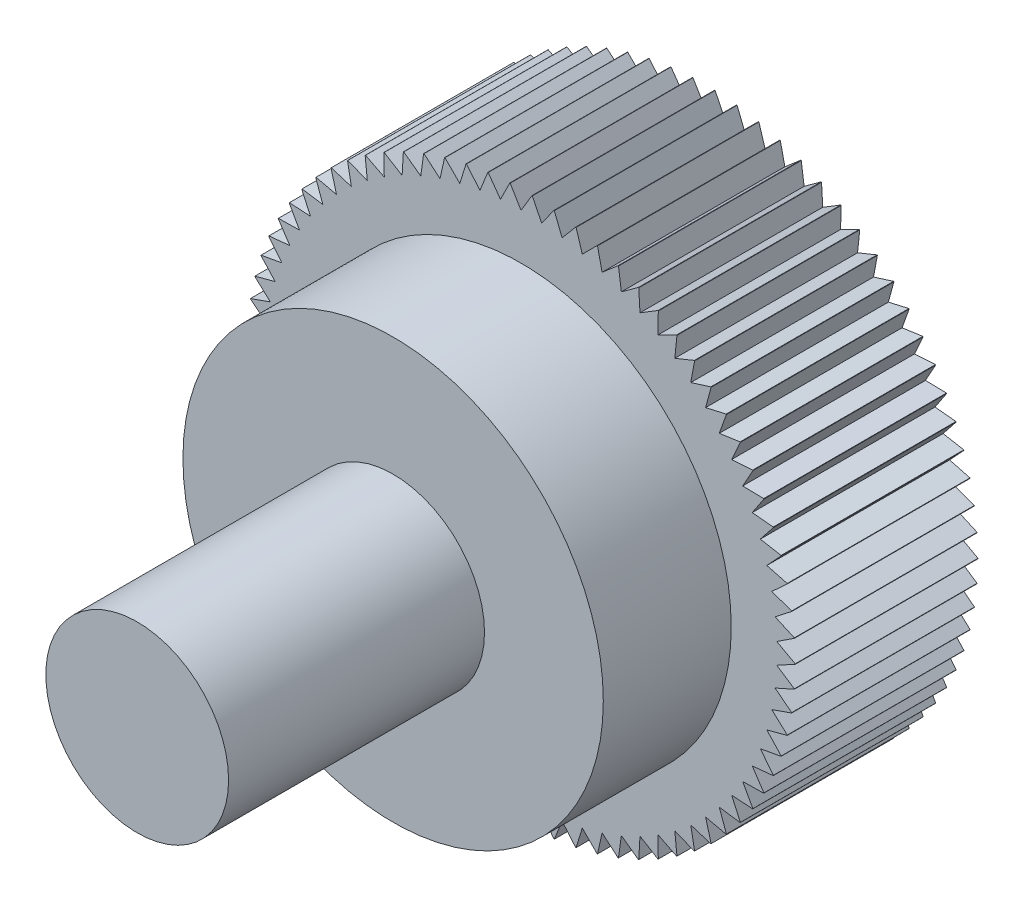
SolidWorks part; units mm, degrees
ref_plane "Front" through (0, 0, 0) normal (0, 0, 1) x (1, 0, 0)
ref_plane "Top" through (0, 0, 0) normal (0, 1, 0) x (1, 0, 0)
ref_plane "Right" through (0, 0, 0) normal (1, 0, 0) x (0, 0, -1)
sketch "Sketch1" plane through (0, 0, 0) normal (0, 0, 1) x (1, 0, 0)
  circle A0 centre (0, 0) radius 7.5
  dimension "D1" = 15
extrude "Extrude1" add sketch "Sketch1" along normal blind 5
sketch "Sketch2" plane through (0, 0, 5) normal (0, 0, 1) x (1, 0, 0)
  circle A0 centre (0, 0) radius 5.75
  dimension "D1" = 11.5
extrude "Extrude2" add sketch "Sketch2" along normal blind 3.5
sketch "Sketch3" plane through (0, 0, 8.5) normal (0, 0, 1) x (1, 0, 0)
  circle A0 centre (0, 0) radius 2.5
  dimension "D1" = 5
extrude "Extrude3" add sketch "Sketch3" along normal blind 7
sketch "Sketch4" plane through (0, 0, 0) normal (0, 0, -1) x (-1, 0, 0)
  line L0 (0, 0) -> (0, 7.5) construction
  line L1 (-0.3, 7.5) -> (0, 7)
  line L2 (0.3, 7.5) -> (0, 7)
  line L3 (-0.3, 7.5) -> (0.3, 7.5)
  line L4 (0.3045, 7.4998) -> (0.5633, 6.9773)
  line L5 (0.9025, 7.4515) -> (0.5633, 6.9773)
  line L6 (0.3045, 7.4998) -> (0.9025, 7.4515)
  line L7 (0.907, 7.451) -> (1.1229, 6.9094)
  line L8 (1.4992, 7.3548) -> (1.1229, 6.9094)
  line L9 (0.907, 7.451) -> (1.4992, 7.3548)
  line L10 (1.5036, 7.3539) -> (1.6752, 6.7966)
  line L11 (2.0862, 7.2103) -> (1.6752, 6.7966)
  line L12 (1.5036, 7.3539) -> (2.0862, 7.2103)
  line L13 (2.0904, 7.209) -> (2.2167, 6.6398)
  line L14 (2.6596, 7.019) -> (2.2167, 6.6398)
  line L15 (2.0904, 7.209) -> (2.6596, 7.019)
  line L16 (2.6638, 7.0174) -> (2.7438, 6.4399)
  line L17 (3.2157, 6.7823) -> (2.7438, 6.4399)
  line L18 (2.6638, 7.0174) -> (3.2157, 6.7823)
  line L19 (3.2198, 6.7803) -> (3.2531, 6.1982)
  line L20 (3.7511, 6.5015) -> (3.2531, 6.1982)
  line L21 (3.2198, 6.7803) -> (3.7511, 6.5015)
  line L22 (3.7549, 6.4993) -> (3.7413, 5.9163)
  line L23 (4.2621, 6.1786) -> (3.7413, 5.9163)
  line L24 (3.7549, 6.4993) -> (4.2621, 6.1786)
  line L25 (4.2657, 6.176) -> (4.2052, 5.5961)
  line L26 (4.7454, 5.8156) -> (4.2052, 5.5961)
  line L27 (4.2657, 6.176) -> (4.7454, 5.8156)
  line L28 (4.7489, 5.8128) -> (4.6419, 5.2396)
  line L29 (5.198, 5.4149) -> (4.6419, 5.2396)
  line L30 (4.7489, 5.8128) -> (5.198, 5.4149)
  line L31 (5.2012, 5.4118) -> (5.0484, 4.8491)
  line L32 (5.6168, 4.9791) -> (5.0484, 4.8491)
  line L33 (5.2012, 5.4118) -> (5.6168, 4.9791)
  line L34 (5.6198, 4.9757) -> (5.4222, 4.4271)
  line L35 (5.9993, 4.511) -> (5.4222, 4.4271)
  line L36 (5.6198, 4.9757) -> (5.9993, 4.511)
  line L37 (6.002, 4.5074) -> (5.7609, 3.9765)
  line L38 (6.3428, 4.0136) -> (5.7609, 3.9765)
  line L39 (6.002, 4.5074) -> (6.3428, 4.0136)
  line L40 (6.3452, 4.0098) -> (6.0622, 3.5)
  line L41 (6.6452, 3.4902) -> (6.0622, 3.5)
  line L42 (6.3452, 4.0098) -> (6.6452, 3.4902)
  line L43 (6.6473, 3.4862) -> (6.3242, 3.0008)
  line L44 (6.9045, 2.9442) -> (6.3242, 3.0008)
  line L45 (6.6473, 3.4862) -> (6.9045, 2.9442)
  line L46 (6.9062, 2.94) -> (6.5451, 2.4822)
  line L47 (7.119, 2.379) -> (6.5451, 2.4822)
  line L48 (6.9062, 2.94) -> (7.119, 2.379)
  line L49 (7.1204, 2.3748) -> (6.7236, 1.9475)
  line L50 (7.2874, 1.7985) -> (6.7236, 1.9475)
  line L51 (7.1204, 2.3748) -> (7.2874, 1.7985)
  line L52 (7.2884, 1.7941) -> (6.8585, 1.4002)
  line L53 (7.4084, 1.2063) -> (6.8585, 1.4002)
  line L54 (7.2884, 1.7941) -> (7.4084, 1.2063)
  line L55 (7.4092, 1.2018) -> (6.949, 0.8438)
  line L56 (7.4815, 0.6062) -> (6.949, 0.8438)
  line L57 (7.4092, 1.2018) -> (7.4815, 0.6062)
  line L58 (7.4818, 0.6018) -> (6.9943, 0.2819)
  line L59 (7.506, 0.0022) -> (6.9943, 0.2819)
  line L60 (7.4818, 0.6018) -> (7.506, 0.0022)
  line L61 (7.506, -0.0022) -> (6.9943, -0.2819)
  line L62 (7.4818, -0.6018) -> (6.9943, -0.2819)
  line L63 (7.506, -0.0022) -> (7.4818, -0.6018)
  line L64 (7.4815, -0.6062) -> (6.949, -0.8438)
  line L65 (7.4092, -1.2018) -> (6.949, -0.8438)
  line L66 (7.4815, -0.6062) -> (7.4092, -1.2018)
  line L67 (7.4084, -1.2063) -> (6.8585, -1.4002)
  line L68 (7.2884, -1.7941) -> (6.8585, -1.4002)
  line L69 (7.4084, -1.2063) -> (7.2884, -1.7941)
  line L70 (7.2874, -1.7985) -> (6.7236, -1.9475)
  line L71 (7.1204, -2.3748) -> (6.7236, -1.9475)
  line L72 (7.2874, -1.7985) -> (7.1204, -2.3748)
  line L73 (7.119, -2.379) -> (6.5451, -2.4822)
  line L74 (6.9062, -2.94) -> (6.5451, -2.4822)
  line L75 (7.119, -2.379) -> (6.9062, -2.94)
  line L76 (6.9045, -2.9442) -> (6.3242, -3.0008)
  line L77 (6.6473, -3.4862) -> (6.3242, -3.0008)
  line L78 (6.9045, -2.9442) -> (6.6473, -3.4862)
  line L79 (6.6452, -3.4902) -> (6.0622, -3.5)
  line L80 (6.3452, -4.0098) -> (6.0622, -3.5)
  line L81 (6.6452, -3.4902) -> (6.3452, -4.0098)
  line L82 (6.3428, -4.0136) -> (5.7609, -3.9765)
  line L83 (6.002, -4.5074) -> (5.7609, -3.9765)
  line L84 (6.3428, -4.0136) -> (6.002, -4.5074)
  line L85 (5.9993, -4.511) -> (5.4222, -4.4271)
  line L86 (5.6198, -4.9757) -> (5.4222, -4.4271)
  line L87 (5.9993, -4.511) -> (5.6198, -4.9757)
  line L88 (5.6168, -4.9791) -> (5.0484, -4.8491)
  line L89 (5.2012, -5.4118) -> (5.0484, -4.8491)
  line L90 (5.6168, -4.9791) -> (5.2012, -5.4118)
  line L91 (5.198, -5.4149) -> (4.6419, -5.2396)
  line L92 (4.7489, -5.8128) -> (4.6419, -5.2396)
  line L93 (5.198, -5.4149) -> (4.7489, -5.8128)
  line L94 (4.7454, -5.8156) -> (4.2052, -5.5961)
  line L95 (4.2657, -6.176) -> (4.2052, -5.5961)
  line L96 (4.7454, -5.8156) -> (4.2657, -6.176)
  line L97 (4.2621, -6.1786) -> (3.7413, -5.9163)
  line L98 (3.7549, -6.4993) -> (3.7413, -5.9163)
  line L99 (4.2621, -6.1786) -> (3.7549, -6.4993)
  line L100 (3.7511, -6.5015) -> (3.2531, -6.1982)
  line L101 (3.2198, -6.7803) -> (3.2531, -6.1982)
  line L102 (3.7511, -6.5015) -> (3.2198, -6.7803)
  line L103 (3.2157, -6.7823) -> (2.7438, -6.4399)
  line L104 (2.6638, -7.0174) -> (2.7438, -6.4399)
  line L105 (3.2157, -6.7823) -> (2.6638, -7.0174)
  line L106 (2.6596, -7.019) -> (2.2167, -6.6398)
  line L107 (2.0904, -7.209) -> (2.2167, -6.6398)
  line L108 (2.6596, -7.019) -> (2.0904, -7.209)
  line L109 (2.0862, -7.2103) -> (1.6752, -6.7966)
  line L110 (1.5036, -7.3539) -> (1.6752, -6.7966)
  line L111 (2.0862, -7.2103) -> (1.5036, -7.3539)
  line L112 (1.4992, -7.3548) -> (1.1229, -6.9094)
  line L113 (0.907, -7.451) -> (1.1229, -6.9094)
  line L114 (1.4992, -7.3548) -> (0.907, -7.451)
  line L115 (0.9025, -7.4515) -> (0.5633, -6.9773)
  line L116 (0.3045, -7.4998) -> (0.5633, -6.9773)
  line L117 (0.9025, -7.4515) -> (0.3045, -7.4998)
  line L118 (0.3, -7.5) -> (0, -7)
  line L119 (-0.3, -7.5) -> (0, -7)
  line L120 (0.3, -7.5) -> (-0.3, -7.5)
  line L121 (-0.3045, -7.4998) -> (-0.5633, -6.9773)
  line L122 (-0.9025, -7.4515) -> (-0.5633, -6.9773)
  line L123 (-0.3045, -7.4998) -> (-0.9025, -7.4515)
  line L124 (-0.907, -7.451) -> (-1.1229, -6.9094)
  line L125 (-1.4992, -7.3548) -> (-1.1229, -6.9094)
  line L126 (-0.907, -7.451) -> (-1.4992, -7.3548)
  line L127 (-1.5036, -7.3539) -> (-1.6752, -6.7966)
  line L128 (-2.0862, -7.2103) -> (-1.6752, -6.7966)
  line L129 (-1.5036, -7.3539) -> (-2.0862, -7.2103)
  line L130 (-2.0904, -7.209) -> (-2.2167, -6.6398)
  line L131 (-2.6596, -7.019) -> (-2.2167, -6.6398)
  line L132 (-2.0904, -7.209) -> (-2.6596, -7.019)
  line L133 (-2.6638, -7.0174) -> (-2.7438, -6.4399)
  line L134 (-3.2157, -6.7823) -> (-2.7438, -6.4399)
  line L135 (-2.6638, -7.0174) -> (-3.2157, -6.7823)
  line L136 (-3.2198, -6.7803) -> (-3.2531, -6.1982)
  line L137 (-3.7511, -6.5015) -> (-3.2531, -6.1982)
  line L138 (-3.2198, -6.7803) -> (-3.7511, -6.5015)
  line L139 (-3.7549, -6.4993) -> (-3.7413, -5.9163)
  line L140 (-4.2621, -6.1786) -> (-3.7413, -5.9163)
  line L141 (-3.7549, -6.4993) -> (-4.2621, -6.1786)
  line L142 (-4.2657, -6.176) -> (-4.2052, -5.5961)
  line L143 (-4.7454, -5.8156) -> (-4.2052, -5.5961)
  line L144 (-4.2657, -6.176) -> (-4.7454, -5.8156)
  line L145 (-4.7489, -5.8128) -> (-4.6419, -5.2396)
  line L146 (-5.198, -5.4149) -> (-4.6419, -5.2396)
  line L147 (-4.7489, -5.8128) -> (-5.198, -5.4149)
  line L148 (-5.2012, -5.4118) -> (-5.0484, -4.8491)
  line L149 (-5.6168, -4.9791) -> (-5.0484, -4.8491)
  line L150 (-5.2012, -5.4118) -> (-5.6168, -4.9791)
  line L151 (-5.6198, -4.9757) -> (-5.4222, -4.4271)
  line L152 (-5.9993, -4.511) -> (-5.4222, -4.4271)
  line L153 (-5.6198, -4.9757) -> (-5.9993, -4.511)
  line L154 (-6.002, -4.5074) -> (-5.7609, -3.9765)
  line L155 (-6.3428, -4.0136) -> (-5.7609, -3.9765)
  line L156 (-6.002, -4.5074) -> (-6.3428, -4.0136)
  line L157 (-6.3452, -4.0098) -> (-6.0622, -3.5)
  line L158 (-6.6452, -3.4902) -> (-6.0622, -3.5)
  line L159 (-6.3452, -4.0098) -> (-6.6452, -3.4902)
  line L160 (-6.6473, -3.4862) -> (-6.3242, -3.0008)
  line L161 (-6.9045, -2.9442) -> (-6.3242, -3.0008)
  line L162 (-6.6473, -3.4862) -> (-6.9045, -2.9442)
  line L163 (-6.9062, -2.94) -> (-6.5451, -2.4822)
  line L164 (-7.119, -2.379) -> (-6.5451, -2.4822)
  line L165 (-6.9062, -2.94) -> (-7.119, -2.379)
  line L166 (-7.1204, -2.3748) -> (-6.7236, -1.9475)
  line L167 (-7.2874, -1.7985) -> (-6.7236, -1.9475)
  line L168 (-7.1204, -2.3748) -> (-7.2874, -1.7985)
  line L169 (-7.2884, -1.7941) -> (-6.8585, -1.4002)
  line L170 (-7.4084, -1.2063) -> (-6.8585, -1.4002)
  line L171 (-7.2884, -1.7941) -> (-7.4084, -1.2063)
  line L172 (-7.4092, -1.2018) -> (-6.949, -0.8438)
  line L173 (-7.4815, -0.6062) -> (-6.949, -0.8438)
  line L174 (-7.4092, -1.2018) -> (-7.4815, -0.6062)
  line L175 (-7.4818, -0.6018) -> (-6.9943, -0.2819)
  line L176 (-7.506, -0.0022) -> (-6.9943, -0.2819)
  line L177 (-7.4818, -0.6018) -> (-7.506, -0.0022)
  line L178 (-7.506, 0.0022) -> (-6.9943, 0.2819)
  line L179 (-7.4818, 0.6018) -> (-6.9943, 0.2819)
  line L180 (-7.506, 0.0022) -> (-7.4818, 0.6018)
  line L181 (-7.4815, 0.6062) -> (-6.949, 0.8438)
  line L182 (-7.4092, 1.2018) -> (-6.949, 0.8438)
  line L183 (-7.4815, 0.6062) -> (-7.4092, 1.2018)
  line L184 (-7.4084, 1.2063) -> (-6.8585, 1.4002)
  line L185 (-7.2884, 1.7941) -> (-6.8585, 1.4002)
  line L186 (-7.4084, 1.2063) -> (-7.2884, 1.7941)
  line L187 (-7.2874, 1.7985) -> (-6.7236, 1.9475)
  line L188 (-7.1204, 2.3748) -> (-6.7236, 1.9475)
  line L189 (-7.2874, 1.7985) -> (-7.1204, 2.3748)
  line L190 (-7.119, 2.379) -> (-6.5451, 2.4822)
  line L191 (-6.9062, 2.94) -> (-6.5451, 2.4822)
  line L192 (-7.119, 2.379) -> (-6.9062, 2.94)
  line L193 (-6.9045, 2.9442) -> (-6.3242, 3.0008)
  line L194 (-6.6473, 3.4862) -> (-6.3242, 3.0008)
  line L195 (-6.9045, 2.9442) -> (-6.6473, 3.4862)
  line L196 (-6.6452, 3.4902) -> (-6.0622, 3.5)
  line L197 (-6.3452, 4.0098) -> (-6.0622, 3.5)
  line L198 (-6.6452, 3.4902) -> (-6.3452, 4.0098)
  line L199 (-6.3428, 4.0136) -> (-5.7609, 3.9765)
  line L200 (-6.002, 4.5074) -> (-5.7609, 3.9765)
  line L201 (-6.3428, 4.0136) -> (-6.002, 4.5074)
  line L202 (-5.9993, 4.511) -> (-5.4222, 4.4271)
  line L203 (-5.6198, 4.9757) -> (-5.4222, 4.4271)
  line L204 (-5.9993, 4.511) -> (-5.6198, 4.9757)
  line L205 (-5.6168, 4.9791) -> (-5.0484, 4.8491)
  line L206 (-5.2012, 5.4118) -> (-5.0484, 4.8491)
  line L207 (-5.6168, 4.9791) -> (-5.2012, 5.4118)
  line L208 (-5.198, 5.4149) -> (-4.6419, 5.2396)
  line L209 (-4.7489, 5.8128) -> (-4.6419, 5.2396)
  line L210 (-5.198, 5.4149) -> (-4.7489, 5.8128)
  line L211 (-4.7454, 5.8156) -> (-4.2052, 5.5961)
  line L212 (-4.2657, 6.176) -> (-4.2052, 5.5961)
  line L213 (-4.7454, 5.8156) -> (-4.2657, 6.176)
  line L214 (-4.2621, 6.1786) -> (-3.7413, 5.9163)
  line L215 (-3.7549, 6.4993) -> (-3.7413, 5.9163)
  line L216 (-4.2621, 6.1786) -> (-3.7549, 6.4993)
  line L217 (-3.7511, 6.5015) -> (-3.2531, 6.1982)
  line L218 (-3.2198, 6.7803) -> (-3.2531, 6.1982)
  line L219 (-3.7511, 6.5015) -> (-3.2198, 6.7803)
  line L220 (-3.2157, 6.7823) -> (-2.7438, 6.4399)
  line L221 (-2.6638, 7.0174) -> (-2.7438, 6.4399)
  line L222 (-3.2157, 6.7823) -> (-2.6638, 7.0174)
  line L223 (-2.6596, 7.019) -> (-2.2167, 6.6398)
  line L224 (-2.0904, 7.209) -> (-2.2167, 6.6398)
  line L225 (-2.6596, 7.019) -> (-2.0904, 7.209)
  line L226 (-2.0862, 7.2103) -> (-1.6752, 6.7966)
  line L227 (-1.5036, 7.3539) -> (-1.6752, 6.7966)
  line L228 (-2.0862, 7.2103) -> (-1.5036, 7.3539)
  line L229 (-1.4992, 7.3548) -> (-1.1229, 6.9094)
  line L230 (-0.907, 7.451) -> (-1.1229, 6.9094)
  line L231 (-1.4992, 7.3548) -> (-0.907, 7.451)
  line L232 (-0.9025, 7.4515) -> (-0.5633, 6.9773)
  line L233 (-0.3045, 7.4998) -> (-0.5633, 6.9773)
  line L234 (-0.9025, 7.4515) -> (-0.3045, 7.4998)
  circle A0 centre (0, 0) radius 7.5 construction
  dimension "D1" = 0.3
  dimension "D2" = 0.5
extrude "Cut-Extrude1" cut sketch "Sketch4" against normal blind 20
sketch "Sketch5" plane through (0, 0, 0) normal (0, 0, -1) x (-1, 0, 0)
  circle A0 centre (0, 0) radius 4
  dimension "D1" = 8
extrude "Cut-Extrude2" cut sketch "Sketch5" against normal blind 0.5
